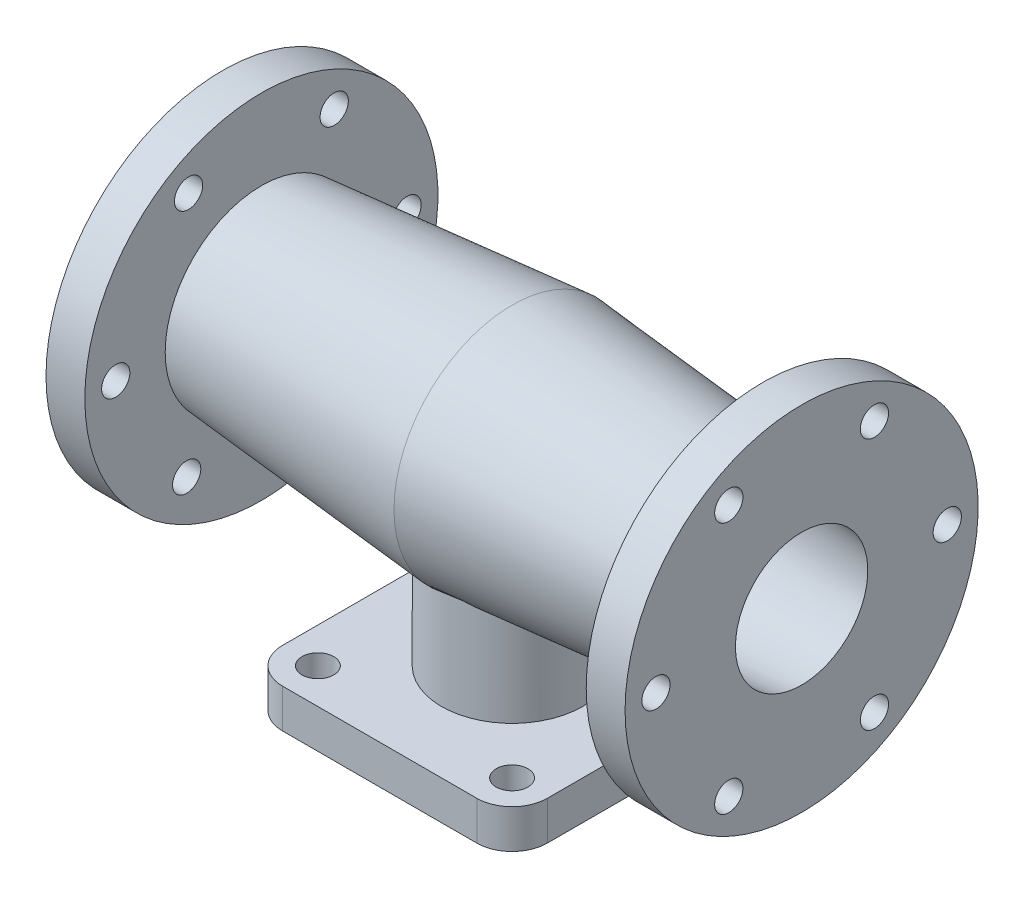
SolidWorks part; units mm, degrees
material "Brass"
ref_plane "Front Plane" through (0, 0, 0) normal (0, 0, 1) x (1, 0, 0)
ref_plane "Top Plane" through (0, 0, 0) normal (0, 1, 0) x (1, 0, 0)
ref_plane "Right Plane" through (0, 0, 0) normal (1, 0, 0) x (0, 0, -1)
sketch "Sketch1" plane through (0, 0, 0) normal (0, 0, 1) x (1, 0, 0)
  line L0 (0, 0) -> (49998.3879, 0) construction
  line L1 (0, 0) -> (0, 49998.3879) construction
  line L2 (-142, -100) -> (-142, -54.482)
  line L3 (-142, -54.482) -> (0, -66.9054)
  line L4 (-142, -100) -> (-164, -100)
  line L5 (-164, -100) -> (-164, -37.5)
  line L6 (-164, -37.5) -> (0, -51.8481)
  line L7 (142, -100) -> (164, -100)
  line L8 (164, -100) -> (164, -37.5)
  line L9 (142, -100) -> (142, -54.482)
  line L10 (142, -54.482) -> (0, -66.9054)
  line L11 (164, -37.5) -> (0, -51.8481)
  dimension "D1" = 284
  dimension "D2" = 22
  dimension "D3" = 5
  dimension "D4" = 15
  dimension "D5" = 200
  dimension "D6" = 75
revolve "Revolve1" add sketch "Sketch1" angle 360 about L0
ref_plane "Plane3" through (0, -110, 0) normal (0, -1, 0) x (-1, 0, 0)
sketch "Sketch3" plane through (0, -110, 0) normal (0, -1, 0) x (-1, 0, 0)
  line L1 (-55, 75) -> (55, 75)
  line L2 (-75, 55) -> (-75, -55)
  line L3 (-55, -75) -> (55, -75)
  line L4 (75, 55) -> (75, -55)
  line L5 (-75, 75) -> (75, -75) construction
  line L6 (-75, -75) -> (75, 75) construction
  circle A0 centre (0, 0) radius 40
  arc A1 (-75, -55) -> (-55, -75) centre (-55, -55) ccw
  arc A2 (55, -75) -> (75, -55) centre (55, -55) ccw
  arc A3 (55, 75) -> (75, 55) centre (55, 55) cw
  arc A4 (-55, 75) -> (-75, 55) centre (-55, 55) ccw
  circle A5 centre (-55, 55) radius 9
  circle A6 centre (-55, -55) radius 9
  circle A7 centre (55, -55) radius 9
  circle A8 centre (55, 55) radius 9
  dimension "D1" = 80
  dimension "D4" = 20
  dimension "D5" = 18
  dimension "D2" = 150
  dimension "D3" = 150
extrude "Boss-Extrude2" add sketch "Sketch3" along normal blind 22 separate body
extrude "Boss-Extrude3" add sketch "Sketch3<3>" against normal up to next contours A0 region at (0, -110, 0)
sketch "Sketch3<3>" plane through (0, -110, 0) normal (0, -1, 0) x (-1, 0, 0) same geometry as "Sketch3"
sketch "Sketch5" plane through (0, 0, 0) normal (0, 0, 1) x (1, 0, 0)
  line L0 (0, 0) -> (0, -50000) construction
  line L3 (55, -110) -> (-55, -110) construction
  line L5 (-22, -45) -> (-22, -95)
  line L6 (-22, -95) -> (-27.5, -95)
  line L7 (-27.5, -95) -> (-27.5, -110)
  line L8 (-110, -110) -> (110, -110) construction
  line L13 (-27.5, -110) -> (0, -110)
  line L14 (0, -110) -> (0, -53.6315)
  line L15 (0, -53.6315) -> (0, -45)
  line L16 (0, -45) -> (-22, -45)
  point P7 (0, -110)
  dimension "D1" = 27.5
  dimension "D2" = 22
  dimension "D3" = 15
  dimension "D4" = 50
revolve "Cut-Revolve4" cut sketch "Sketch5" angle 360 about L0
sketch "Sketch11" plane through (164, 0, 0) normal (1, 0, 0) x (0, 0, -1)
  circle A0 centre (0, 0) radius 82.5 construction
  circle A1 centre (-82.5, 0) radius 8
  circle A2 centre (0, 0) radius 82.5 construction
  circle A3 centre (-41.25, 71.4471) radius 8
  circle A4 centre (0, 0) radius 82.5 construction
  circle A5 centre (41.25, 71.4471) radius 8
  circle A6 centre (0, 0) radius 82.5 construction
  circle A7 centre (82.5, 0) radius 8
  circle A8 centre (0, 0) radius 82.5 construction
  circle A9 centre (41.25, -71.4471) radius 8
  circle A10 centre (0, 0) radius 82.5 construction
  circle A11 centre (-41.25, -71.4471) radius 8
  circle A12 centre (82.5, 0) radius 8
  circle A13 centre (41.25, -71.4471) radius 8
  circle A14 centre (-41.25, -71.4471) radius 8
  circle A15 centre (-82.5, 0) radius 8
  circle A16 centre (-41.25, 71.4471) radius 8
  circle A17 centre (41.25, 71.4471) radius 8
  point P23 (0, 0)
  point P34 (0, 0)
  dimension "D1" = 165
  dimension "D2" = 16
  dimension "D4" = 6
  dimension "D3" = 6
extrude "Cut-Extrude3" cut sketch "Sketch11" against normal through all both contours A3 | A5 | A1 | A7 region at (164, 0, 82.5) region at (164, 71.4471, 41.25) region at (164, 71.4471, -41.25) region at (164, 0, -82.5)
extrude "Cut-Extrude5" cut sketch "Sketch11<4>" against normal up to next (22 mm away) contours A11 | A9 region at (164, -71.4471, 41.25)
sketch "Sketch11<4>" plane through (164, 0, 0) normal (1, 0, 0) x (0, 0, -1) same geometry as "Sketch11"
hole_wizard "Ø16.0mm Dowel Hole3" positions "3DSketch2" profile "Sketch16" hole size "Ø16.0" standard "ISO" end condition up to next
sketch3d "3DSketch2"
  point P0 (-164, -66.0875, -37.1338)
  point P2 (-164, -67.2389, 42.3153)
sketch "Sketch16" plane through (-164, -66.0875, -37.1338) normal (0, 1, 0) x (0, 0, 1)
  line L0 (0, 0) -> (0, 22.001)
  line L1 (0, 22.001) -> (8, 22.001)
  line L2 (8, 22.001) -> (8, 0)
  line L5 (8, 0) -> (0, 0)
  line L11 (0, -6.35) -> (0, 107.95) construction
  dimension "Thru Hole Dia." = 16
  dimension "Thru Hole Depth" = 22.001
